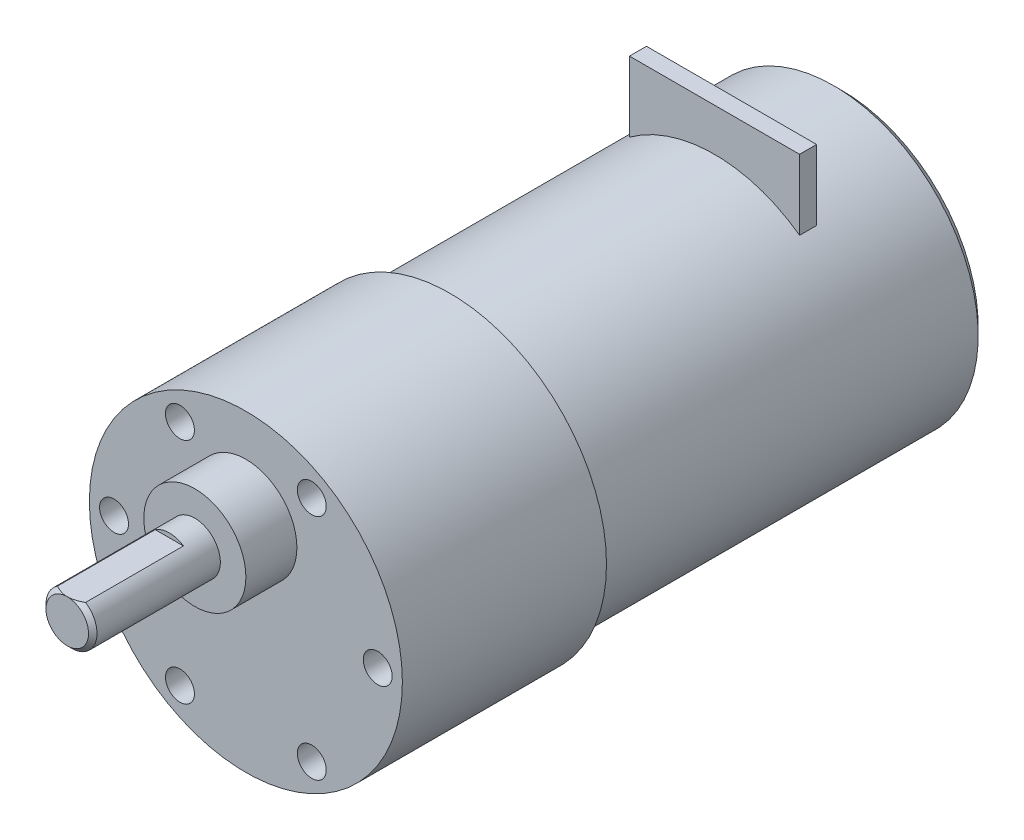
SolidWorks part; units mm, degrees
ref_plane "Front Plane" through (0, 0, 0) normal (0, 0, 1) x (1, 0, 0)
ref_plane "Top Plane" through (0, 0, 0) normal (0, 1, 0) x (1, 0, 0)
ref_plane "Right Plane" through (0, 0, 0) normal (1, 0, 0) x (0, 0, -1)
sketch "Sketch2" plane through (0, 0, 0) normal (0, 0, 1) x (1, 0, 0)
  circle A0 centre (0, 0) radius 18.4
  dimension "D1" = 36.8
extrude "Boss-Extrude1" add sketch "Sketch2" along normal blind 24
sketch "Sketch3" plane through (0, 0, 0) normal (0, 0, -1) x (-1, 0, 0)
  circle A0 centre (0, 0) radius 17
  dimension "D1" = 34
extrude "Boss-Extrude2" add sketch "Sketch3" along normal blind 46.1
chamfer "Chamfer1" distance 1 angle 45 1 edges at (-17, 0, -46.1)
sketch "Sketch6" plane through (0, 0, 24) normal (0, 0, 1) x (1, 0, 0)
  circle A0 centre (0, 7.5) radius 6
  circle A1 centre (0, 0) radius 18.4 construction
  dimension "D1" = 12
  dimension "D2" = 7.5
extrude "Boss-Extrude5" add sketch "Sketch6" along normal blind 6
sketch "Sketch7" plane through (0, 0, 30) normal (0, 0, 1) x (1, 0, 0)
  circle A0 centre (0, 7.5) radius 3
  dimension "D1" = 6
extrude "Boss-Extrude6" add sketch "Sketch7" along normal blind 15
sketch "Sketch8" plane through (0, 0, 45) normal (0, 0, 1) x (1, 0, 0)
  line L0 (-1.6583, 10) -> (1.6583, 10)
  circle A0 centre (0, 7.5) radius 3 construction
  circle A1 centre (0, 7.5) radius 3
  circle M3 centre (0, 7.5) radius 3
  dimension "D1" = 2.5
extrude "Cut-Extrude1" cut sketch "Sketch8" against normal blind 12 contours L0 M3 region at (0, 10.2015, 45)
chamfer "Chamfer2" distance 0.5 angle 45 1 edges at (0, 4.5, 45)
sketch "Sketch9" plane through (0, 0, 24) normal (0, 0, 1) x (1, 0, 0)
  line L0 (0, 0) -> (-15.5, 0) construction
  circle A0 centre (0, 0) radius 15.5 construction
  point P3 (-15.5, 0)
  dimension "D1" = 31
hole_wizard "M3 Clearance Hole1" positions "Sketch9" profile "Sketch10" hole size "M3" standard "ANSI Metric"
sketch "Sketch10" plane through (-15.5, 0, 24) normal (1, 0, 0) x (0, -1, 0)
  line L0 (0, 0) -> (0, 4.5215)
  line L1 (0, 4.5215) -> (1.7, 3.5)
  line L2 (1.7, 3.5) -> (1.7, 0)
  line L5 (1.7, 0) -> (0, 0)
  line L10 (0, 4.5215) -> (-1.7, 3.5) construction
  line L11 (0, -6.35) -> (0, 107.95) construction
  dimension "Hole Dia." = 3.4
  dimension "Hole Depth" = 3.5
  dimension "Drill Angle" = 118
pattern_circular "CirPattern1" count 6 over 360 about axis through (0, 0, 24) along (0, 0, -1) of "M3 Clearance Hole1"
sketch "Sketch11" plane through (0, 0, 0) normal (0, 1, 0) x (1, 0, 0)
  line L0 (16, 46.1) -> (-16, 46.1) construction
  line L1 (-10, 33.1) -> (10, 33.1)
  line L2 (-10, 33.1) -> (-10, 31.1)
  line L3 (-10, 31.1) -> (10, 31.1)
  line L4 (10, 33.1) -> (10, 31.1)
  point P4 (0, 31.1)
  dimension "D1" = 15
  dimension "D2" = 2
  dimension "D3" = 20
extrude "Boss-Extrude7" add sketch "Sketch11" along normal blind 22
